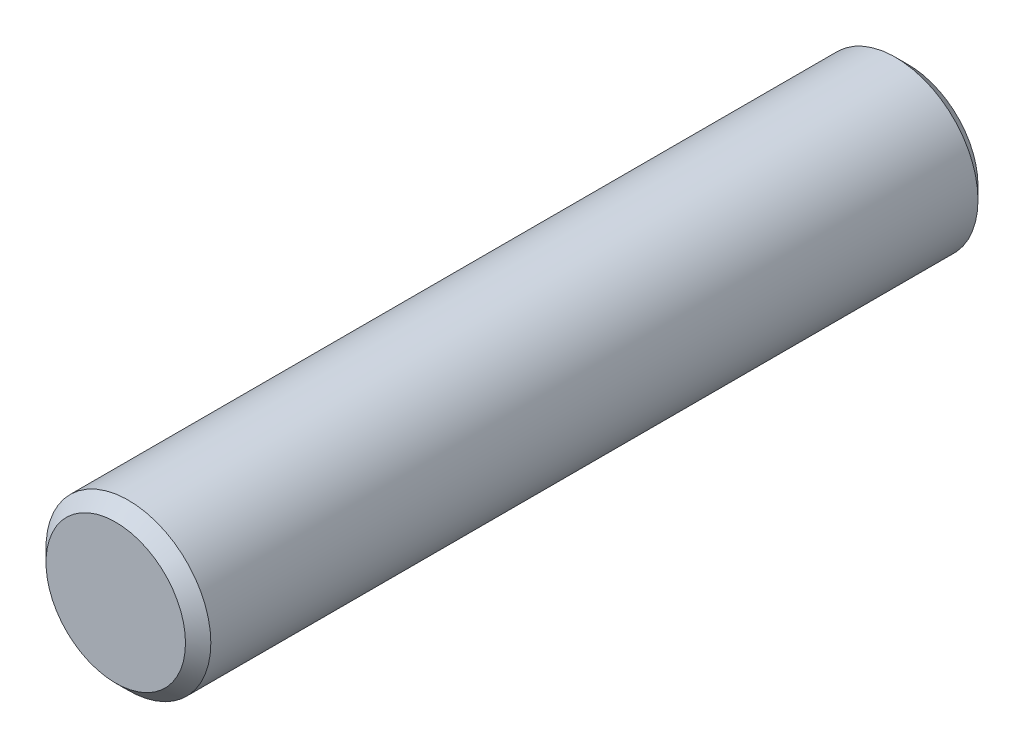
SolidWorks part; units mm, degrees
material "Plain Carbon Steel"
ref_plane "Front Plane" through (0, 0, 0) normal (0, 0, 1) x (1, 0, 0)
ref_plane "Top Plane" through (0, 0, 0) normal (0, 1, 0) x (1, 0, 0)
ref_plane "Right Plane" through (0, 0, 0) normal (1, 0, 0) x (0, 0, -1)
ref_axis "X-axis" through (-88.99, 0, 0) along (1, 0, 0)
ref_axis "Y-axis" through (0, 55, 0) along (0, -1, 0)
ref_axis "Z-axis" through (0, 0, -88.99) along (0, 0, 1)
sketch "Sketch1" plane through (0, 0, 0) normal (0, 0, 1) x (1, 0, 0)
  circle A0 centre (0, 0) radius 1.651
  dimension "D1" = 3.302
extrude "Boss-Extrude1" add sketch "Sketch1" against normal blind 15.875
chamfer "Chamfer1" distance 0.254 angle 45 2 edges at (1.651, 0, -15.875) (1.651, 0, 0)
